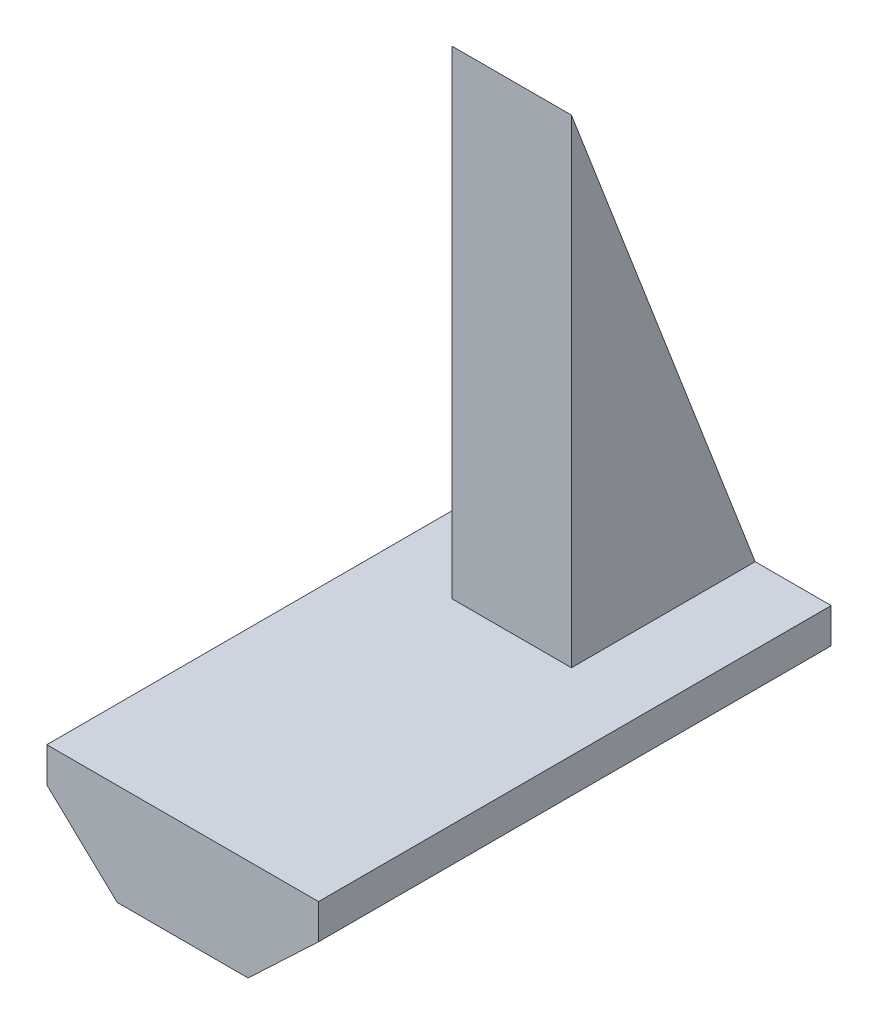
SolidWorks part; units mm, degrees
ref_plane "Front Plane" through (0, 0, 0) normal (0, 0, 1) x (1, 0, 0)
ref_plane "Top Plane" through (0, 0, 0) normal (0, 1, 0) x (1, 0, 0)
ref_plane "Right Plane" through (0, 0, 0) normal (1, 0, 0) x (0, 0, -1)
sketch "Sketch1" plane through (0, 0, 0) normal (0, 0, 1) x (1, 0, 0)
  line L1 (7.95, 0) -> (7.95, -2.04)
  line L2 (7.95, -2.04) -> (3.8283, -5.9337)
  line L6 (3.8283, -5.9337) -> (-3.8283, -5.9337)
  line L7 (0, 0) -> (0, 9.9098) construction
  line L8 (-7.95, -2.04) -> (-3.8283, -5.9337)
  line L9 (-7.95, 0) -> (-7.95, -2.04)
  line L10 (-7.95, 0) -> (7.95, 0)
  point P9 (0, -5.9337)
  dimension "D1" = 15.9
  dimension "D3" = 2.04
  dimension "D4" = 5.67
extrude "Boss-Extrude1" add sketch "Sketch1" along normal blind 30 contours L10 L1 L2 L6 L8 L9
ref_plane "Plane1" through (0, 0, 0) normal (-1, 0, 0) x (0, 0, 1)
sketch "Sketch2" plane through (0, 0, 0) normal (-1, 0, 0) x (0, 0, 1)
  line L0 (0, 0) -> (10.751, 28.0074)
  line L1 (10.751, 28.0074) -> (10.751, 0)
  line L2 (30, 0) -> (0, 0) construction
  line L3 (10.751, 0) -> (0, 0)
  dimension "D1" = 69
  dimension "D2" = 30
extrude "Boss-Extrude2" add sketch "Sketch2" along normal mid plane 7 contours L3 L0 L1
ref_plane "Plane2" through (0, 1.7918, -4.6679) normal (0, 0.3584, -0.9336) x (-1, 0, 0)
